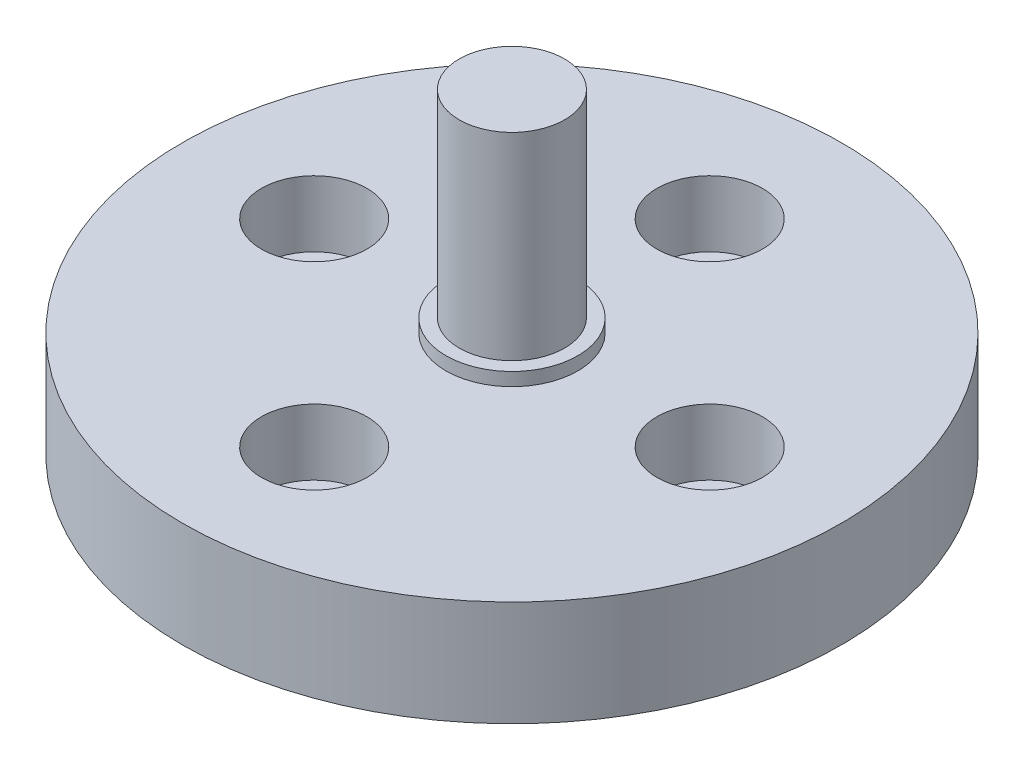
SolidWorks part; units mm, degrees
ref_plane "Front Plane" through (0, 0, 0) normal (0, 0, 1) x (1, 0, 0)
ref_plane "Top Plane" through (0, 0, 0) normal (0, 1, 0) x (1, 0, 0)
ref_plane "Right Plane" through (0, 0, 0) normal (1, 0, 0) x (0, 0, -1)
sketch "Sketch1" plane through (0, 0, 0) normal (0, 1, 0) x (1, 0, 0)
  circle A0 centre (0, 0) radius 25
  dimension "D1" = 50
extrude "Boss-Extrude1" add sketch "Sketch1" along normal blind 8
sketch "Sketch2" plane through (0, 8, 0) normal (0, 1, 0) x (1, 0, 0)
  circle A0 centre (0, 0) radius 5
  dimension "D1" = 10
extrude "Boss-Extrude2" add sketch "Sketch2" along normal blind 1
sketch "Sketch3" plane through (0, 9, 0) normal (0, 1, 0) x (1, 0, 0)
  circle A0 centre (0, 0) radius 4
  dimension "D1" = 8
extrude "Boss-Extrude3" add sketch "Sketch3" along normal blind 15
hole_wizard "Hole1" positions "Sketch7" profile "Sketch6" legacy end condition through all
sketch "Sketch7" plane through (0, 8, 0) normal (0, 1, 0) x (1, 0, 0)
  point P0 (-15, 0)
  point P2 (0, 15)
  point P4 (15, 0)
  point P6 (0, -15)
  dimension "D1" = 15
  dimension "D2" = 15
  dimension "D3" = 15
  dimension "D4" = 15
sketch "Sketch6" plane through (-15, 8, 0) normal (1, 0, 0) x (0, 0, 1)
  line L0 (0, 0) -> (0, 8)
  line L1 (0, 8) -> (2, 8)
  line L2 (2, 8) -> (2, 5)
  line L3 (2, 5) -> (4, 5)
  line L4 (4, 5) -> (4, 0)
  line L5 (4, 0) -> (0, 0)
  line L6 (0, 110) -> (0, -10) construction
  dimension "Diameter" = 4
  dimension "Depth" = 8
  dimension "C-Bore Diameter" = 8
  dimension "C-Bore Depth" = 5
